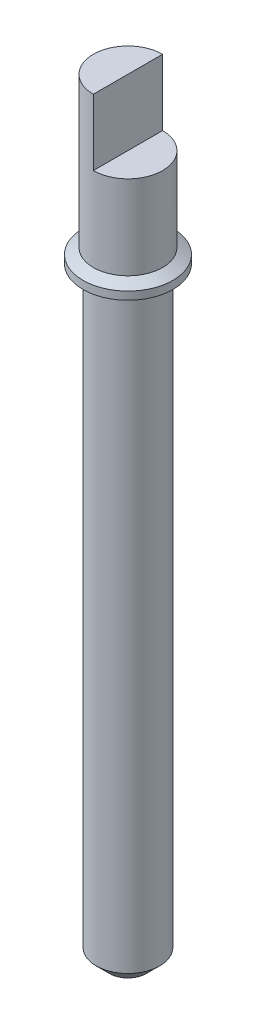
SolidWorks part; units mm, degrees
ref_plane "Front Plane" through (0, 0, 0) normal (0, 0, 1) x (1, 0, 0)
ref_plane "Top Plane" through (0, 0, 0) normal (0, 1, 0) x (1, 0, 0)
ref_plane "Right Plane" through (0, 0, 0) normal (1, 0, 0) x (0, 0, -1)
sketch "Sketch1" plane through (0, 0, 0) normal (0, 1, 0) x (1, 0, 0)
  circle A0 centre (0, 0) radius 0.6
extrude "Boss-Extrude1" add sketch "Sketch1" along normal blind 11.45
cosmetic thread "Cosmetic Thread1" parameters "D1"=9.75, "D2"=1.19
chamfer "Chamfer1" distance 0.25 angle 45 1 edges at (0, 0, 0.6)
sketch "Sketch3" plane through (0, 11.45, 0) normal (0, 1, 0) x (1, 0, 0)
  circle A0 centre (0, 0) radius 0.85
extrude "Boss-Extrude2" add sketch "Sketch3" along normal blind 0.15
sketch "Sketch4" plane through (0, 11.6, 0) normal (0, 1, 0) x (1, 0, 0)
  circle A0 centre (0, 0) radius 0.655
extrude "Boss-Extrude3" add sketch "Sketch4" along normal blind 2.95
sketch "Sketch5" plane through (0, 14.55, 0) normal (0, 1, 0) x (1, 0, 0)
  line L1 (0, 0.9193) -> (0.9651, 0.9193)
  line L2 (0, 0.9193) -> (0, -0.9407)
  line L3 (0, -0.9407) -> (0.9651, -0.9407)
  line L4 (0.9651, 0.9193) -> (0.9651, -0.9407)
extrude "Cut-Extrude1" cut sketch "Sketch5" against normal blind 1.25
chamfer "Chamfer2" distance 0.195 angle 30 1 edges at (0, 11.6, 0.655) first distance on face at (0, 11.6, 0.655)
chamfer "Chamfer3" distance 0.144 angle 60 1 edges at (0, 11.45, 0.6) first distance on face at (0, 0.25, 0.6)
